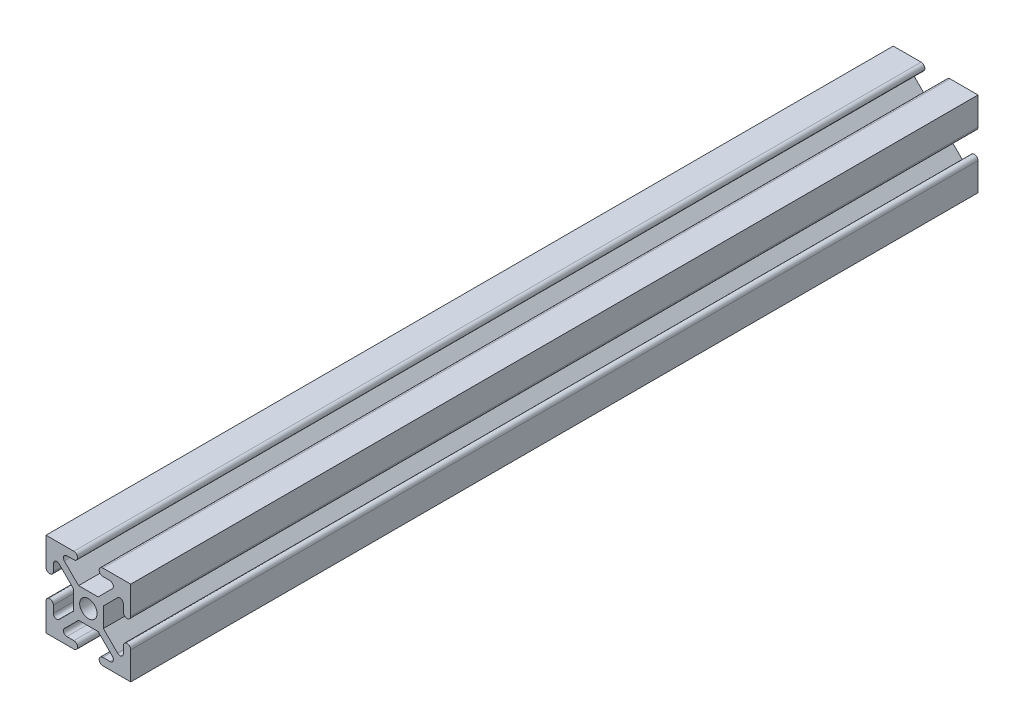
SolidWorks part; units mm, degrees
ref_plane "Front Plane" through (0, 0, 0) normal (0, 0, 1) x (1, 0, 0)
ref_plane "Top Plane" through (0, 0, 0) normal (0, 1, 0) x (1, 0, 0)
ref_plane "Right Plane" through (0, 0, 0) normal (1, 0, 0) x (0, 0, -1)
sketch "Sketch1" plane through (0, 0, 0) normal (0, 0, 1) x (1, 0, 0)
  line L2 (-12.7, -12.7) -> (-4.3434, -12.7)
  line L3 (-4.3434, -10.4902) -> (-6.4748, -10.4902)
  line L4 (-7.1932, -8.7558) -> (-2.9332, -4.4958)
  line L5 (-2.9332, -4.4958) -> (2.9332, -4.4958)
  line L6 (2.9332, -4.4958) -> (7.1932, -8.7558)
  line L7 (6.4748, -10.4902) -> (4.3434, -10.4902)
  line L8 (4.3434, -12.7) -> (12.7, -12.7)
  line L11 (12.7, -12.7) -> (12.7, -4.3434)
  line L12 (10.4902, -4.3434) -> (10.4902, -6.4748)
  line L13 (8.7558, -7.1932) -> (4.4958, -2.9332)
  line L14 (4.4958, -2.9332) -> (4.4958, 2.9332)
  line L15 (4.4958, 2.9332) -> (8.7558, 7.1932)
  line L16 (10.4902, 6.4748) -> (10.4902, 4.3434)
  line L17 (12.7, 4.3434) -> (12.7, 12.7)
  line L20 (12.7, 12.7) -> (4.3434, 12.7)
  line L21 (4.3434, 10.4902) -> (6.4748, 10.4902)
  line L22 (7.1932, 8.7558) -> (2.9332, 4.4958)
  line L23 (2.9332, 4.4958) -> (-2.9332, 4.4958)
  line L24 (-2.9332, 4.4958) -> (-7.1932, 8.7558)
  line L25 (-6.4748, 10.4902) -> (-4.3434, 10.4902)
  line L26 (-4.3434, 12.7) -> (-12.7, 12.7)
  line L29 (-12.7, 12.7) -> (-12.7, 4.3434)
  line L30 (-10.4902, 4.3434) -> (-10.4902, 6.4748)
  line L31 (-8.7558, 7.1932) -> (-4.4958, 2.9332)
  line L32 (-4.4958, 2.9332) -> (-4.4958, -2.9332)
  line L33 (-4.4958, -2.9332) -> (-8.7558, -7.1932)
  line L34 (-10.4902, -6.4748) -> (-10.4902, -4.3434)
  line L35 (-12.7, -4.3434) -> (-12.7, -12.7)
  circle A0 centre (0, 0) radius 2.6035
  arc A6 (-4.3434, -12.7) -> (-4.3434, -10.4902) centre (-4.3434, -11.5951) ccw
  arc A7 (-6.4748, -10.4902) -> (-7.1932, -8.7558) centre (-6.4748, -9.4742) cw
  arc A10 (7.1932, -8.7558) -> (6.4748, -10.4902) centre (6.4748, -9.4742) cw
  arc A11 (4.3434, -10.4902) -> (4.3434, -12.7) centre (4.3434, -11.5951) ccw
  arc A17 (12.7, -4.3434) -> (10.4902, -4.3434) centre (11.5951, -4.3434) ccw
  arc A18 (10.4902, -6.4748) -> (8.7558, -7.1932) centre (9.4742, -6.4748) cw
  arc A21 (8.7558, 7.1932) -> (10.4902, 6.4748) centre (9.4742, 6.4748) cw
  arc A22 (10.4902, 4.3434) -> (12.7, 4.3434) centre (11.5951, 4.3434) ccw
  arc A28 (4.3434, 12.7) -> (4.3434, 10.4902) centre (4.3434, 11.5951) ccw
  arc A29 (6.4748, 10.4902) -> (7.1932, 8.7558) centre (6.4748, 9.4742) cw
  arc A32 (-7.1932, 8.7558) -> (-6.4748, 10.4902) centre (-6.4748, 9.4742) cw
  arc A33 (-4.3434, 10.4902) -> (-4.3434, 12.7) centre (-4.3434, 11.5951) ccw
  arc A39 (-12.7, 4.3434) -> (-10.4902, 4.3434) centre (-11.5951, 4.3434) ccw
  arc A40 (-10.4902, 6.4748) -> (-8.7558, 7.1932) centre (-9.4742, 6.4748) cw
  arc A43 (-8.7558, -7.1932) -> (-10.4902, -6.4748) centre (-9.4742, -6.4748) cw
  arc A44 (-10.4902, -4.3434) -> (-12.7, -4.3434) centre (-11.5951, -4.3434) ccw
  point P101 (-4.4958, 0)
  point P102 (0, 4.4958)
  point P103 (4.4958, 0)
  point P127 (0, -4.4958)
extrude "Boss-Extrude1" add sketch "Sketch1" against normal blind 254
